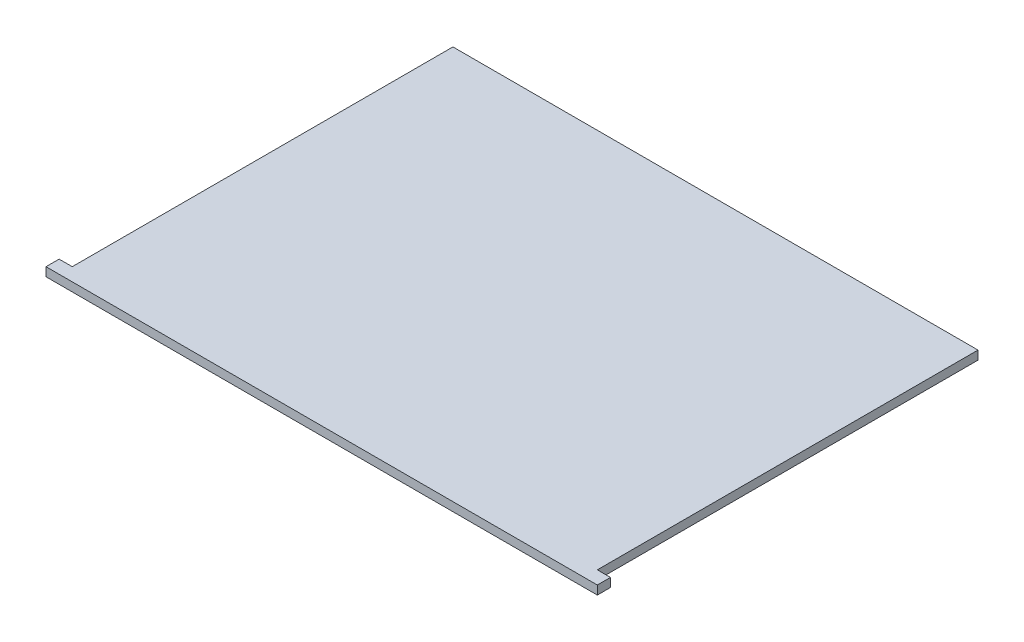
SolidWorks part; units mm, degrees
material "ABS"
ref_plane "Front Plane" through (0, 0, 0) normal (0, 0, 1) x (1, 0, 0)
ref_plane "Top Plane" through (0, 0, 0) normal (0, 1, 0) x (1, 0, 0)
ref_plane "Right Plane" through (0, 0, 0) normal (1, 0, 0) x (0, 0, -1)
sketch "Sketch1" plane through (0, 0, 0) normal (0, 1, 0) x (1, 0, 0)
  line L1 (-30, -22.5) -> (30, -22.5)
  line L3 (-30, 22.5) -> (30, 22.5)
  line L5 (-30, -22.5) -> (30, 22.5) construction
  line L6 (-30, 22.5) -> (30, -22.5) construction
  line L17 (-30, 22.5) -> (-30, -21)
  line L18 (-31.5, -21) -> (-31.5, -22.5)
  line L19 (-31.5, -22.5) -> (-30, -22.5)
  line L20 (-30, -21) -> (-31.5, -21)
  line L21 (30, 22.5) -> (30, -21)
  line L22 (30, -21) -> (31.5, -21)
  line L23 (31.5, -21) -> (31.5, -22.5)
  line L24 (31.5, -22.5) -> (30, -22.5)
  point P0 (0, 0)
  dimension "D1" = 1.5
  dimension "D2" = 1.5
  dimension "D3" = 60
  dimension "D4" = 45
  dimension "D5" = 1.5
  dimension "D6" = 1.5
extrude "Boss-Extrude1" add sketch "Sketch1" along normal blind 1
